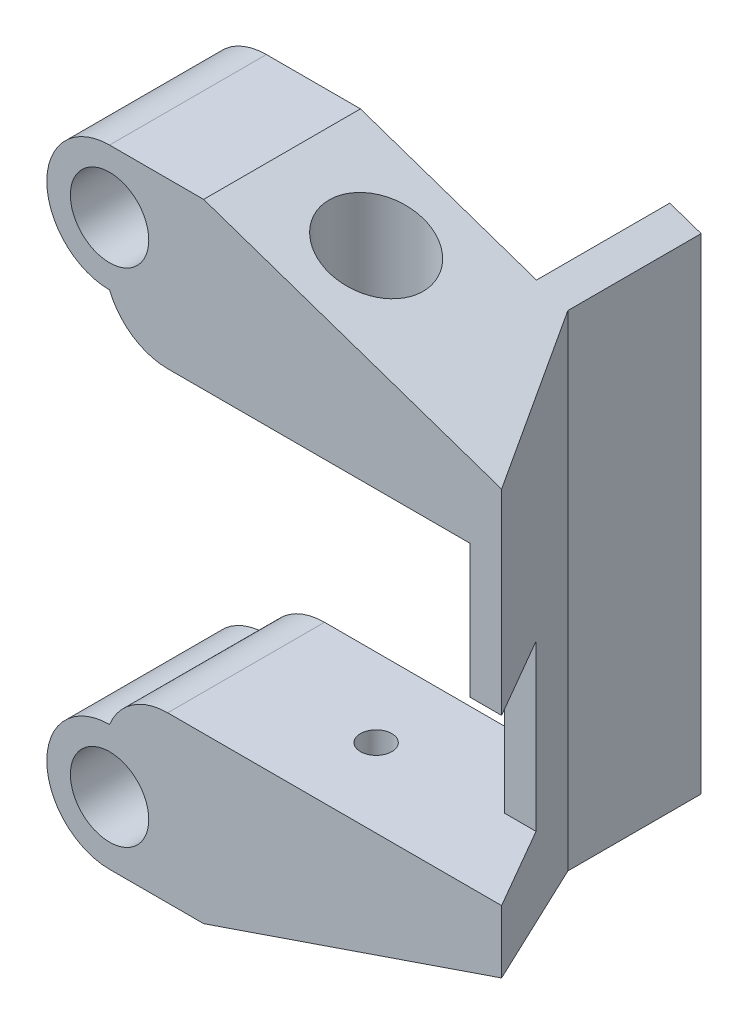
SolidWorks part; units mm, degrees
ref_plane "Alzado" through (0, 0, 0) normal (0, 0, 1) x (1, 0, 0)
ref_plane "Planta" through (0, 0, 0) normal (0, 1, 0) x (1, 0, 0)
ref_plane "Vista lateral" through (0, 0, 0) normal (1, 0, 0) x (0, 0, -1)
sketch "Croquis1" plane through (0, 0, 0) normal (0, 0, 1) x (1, 0, 0)
  line L5 (-106.2316, 22.7007) -> (-131.2316, 22.7007)
  line L6 (-131.2316, 22.7007) -> (-131.2316, 20.2007)
  line L7 (-106.2316, 22.7007) -> (-106.2316, 18.7007)
  line L8 (-106.2316, 18.7007) -> (-125.2316, 18.7007)
  line L9 (-125.2316, 18.7007) -> (-125.2316, 12.2007)
  line L10 (-125.2316, 12.2007) -> (-131.2316, 12.2007)
  circle A0 centre (-131.2316, 16.2007) radius 2.5
  arc A2 (-131.2316, 20.2007) -> (-131.2316, 12.2007) centre (-131.2316, 16.2007) ccw
  dimension "D1" = 4
  dimension "D2" = 5
  dimension "D3" = 6
  dimension "D4" = 6.5
  dimension "D5" = 25
  dimension "D6" = 6.5
  dimension "D7" = 19
  dimension "D8" = 2.5
extrude "Saliente-Extruir1" add sketch "Croquis1" along normal blind 10
sketch "Croquis2" plane through (0, 18.7007, 0) normal (0, -1, 0) x (1, 0, 0)
  line L1 (-106.2316, 0) -> (-106.2316, 10)
  line L2 (-106.2316, 10) -> (-112.0051, 0)
  line L4 (-112.0051, 0) -> (-106.2316, 0)
  line L6 (-106.2316, 10) -> (-106.2316, 0) construction
  circle A0 centre (-119.2316, 5) radius 1
  dimension "D1" = 13
  dimension "D2" = 30
  dimension "D3" = 0
extrude "Cortar-Extruir1" cut sketch "Croquis2" against normal up to vertex (4 mm away) up to point (-106.2316, 22.7007, 10)
sketch "Croquis3" plane through (0, 18.7007, 0) normal (0, -1, 0) x (1, 0, 0)
  line L0 (-106.2316, 10) -> (-108.2316, 10)
  line L1 (-108.2316, 10) -> (-114.0051, 0)
  line L2 (-114.0051, 0) -> (-112.0051, 0)
  line L3 (-106.2316, 10) -> (-112.0051, 0)
  dimension "D1" = 2
  dimension "D2" = 2
extrude "Saliente-Extruir2" add sketch "Croquis3" against normal blind 13.5
sketch "Croquis4" plane through (0, 18.7007, 0) normal (0, -1, 0) x (1, 0, 0)
  circle A0 centre (-119.2316, 5) radius 3
extrude "Cortar-Extruir2" cut sketch "Croquis4" against normal blind 1
sketch "Croquis6" plane through (0, 18.7007, 0) normal (0, -1, 0) x (1, 0, 0)
  line L0 (-125.2316, 10) -> (-106.2316, 10)
  line L1 (-106.2316, 10) -> (-112.0051, 0)
  line L2 (-112.0051, 0) -> (-125.2316, 0)
  line L3 (-125.2316, 0) -> (-125.2316, 10)
  circle A0 centre (-119.2316, 5) radius 3
extrude "Saliente-Extruir3" add sketch "Croquis6" along normal up to vertex (6.5 mm away) up to point (-125.2316, 12.2007, 10)
sketch "Croquis7" plane through (0, 0, 10) normal (0, 0, 1) x (1, 0, 0)
  line L1 (-106.2316, 12.2007) -> (-106.2316, 32.2007) construction
  line L4 (-106.2316, 18.7007) -> (-106.2316, 12.2007)
  line L5 (-106.2316, 12.2007) -> (-125.2316, 12.2007)
  line L6 (-131.2316, 12.2007) -> (-106.2316, 12.2007) construction
  line L7 (-125.2316, 12.2007) -> (-106.2316, 18.7007)
  dimension "D1" = 19
  dimension "D2" = 6.5
extrude "Cortar-Extruir4" cut sketch "Croquis7" against normal blind 10
sketch "Croquis5" plane through (0, 0, 10) normal (0, 0, 1) x (1, 0, 0)
  line L0 (-106.2316, 18.7007) -> (-106.2316, 32.2007) construction
  line L1 (-108.2316, 22.7007) -> (-106.2316, 22.7007)
  line L2 (-108.2316, 22.7007) -> (-108.2316, 33.2007)
  line L3 (-108.2316, 33.2007) -> (-106.2316, 33.2007)
  line L4 (-106.2316, 22.7007) -> (-106.2316, 33.2007)
  dimension "D1" = 10.5
sketch "Croquis8" plane through (0, 0, 0) normal (0, 0, -1) x (-1, 0, 0)
  line L0 (112.0051, 16.7255) -> (112.0051, 32.2007)
  line L1 (112.0051, 32.2007) -> (114.0051, 32.2007)
  line L2 (114.0051, 32.2007) -> (114.0051, 22.7007)
  line L3 (114.0051, 22.7007) -> (114.0051, 16.0413)
  line L4 (112.0051, 16.7255) -> (125.2316, 12.2007) construction
  line L5 (114.0051, 16.0413) -> (112.0051, 16.7255)
extrude "Saliente-Extruir4" add sketch "Croquis8" along normal blind 8.5
mirror "Simetría1" about plane through (0, 32.2007, 0) normal (0, -1, 0) of bodies 110
extrude "Cortar-Extruir5" cut sketch "Croquis5" along direction (-0.5, 0, -0.866) on the side against the normal blind 6
fillet "Redondeo1" radius 4 2 edges at (-131.2316, 41.7007, 5) (-131.2316, 22.7007, 5)
